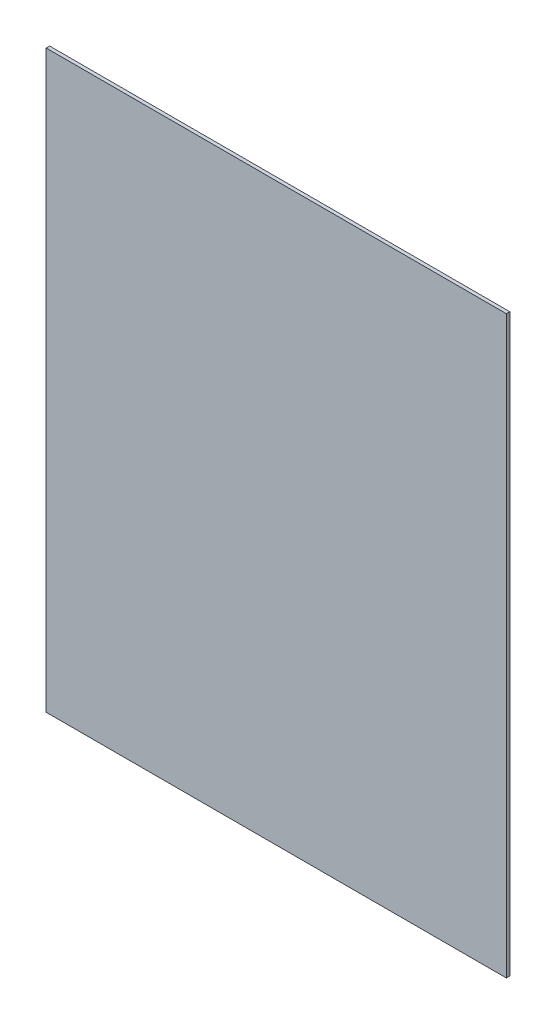
SolidWorks part; units mm, degrees
ref_plane "Plano frontal" through (0, 0, 0) normal (0, 0, 1) x (1, 0, 0)
ref_plane "Plano superior" through (0, 0, 0) normal (0, 1, 0) x (1, 0, 0)
ref_plane "Plano direito" through (0, 0, 0) normal (1, 0, 0) x (0, 0, -1)
sketch "Esboço1" plane through (0, 0, 0) normal (0, 0, 1) x (1, 0, 0)
  line L1 (-200, -250) -> (200, -250)
  line L2 (-200, -250) -> (-200, 250)
  line L3 (-200, 250) -> (200, 250)
  line L4 (200, -250) -> (200, 250)
  line L5 (-200, -250) -> (200, 250) construction
  line L6 (-200, 250) -> (200, -250) construction
  point P0 (0, 0)
  dimension "D1" = 500
  dimension "D2" = 400
extrude "Ressalto-extrusão1" add sketch "Esboço1" along normal blind 3
